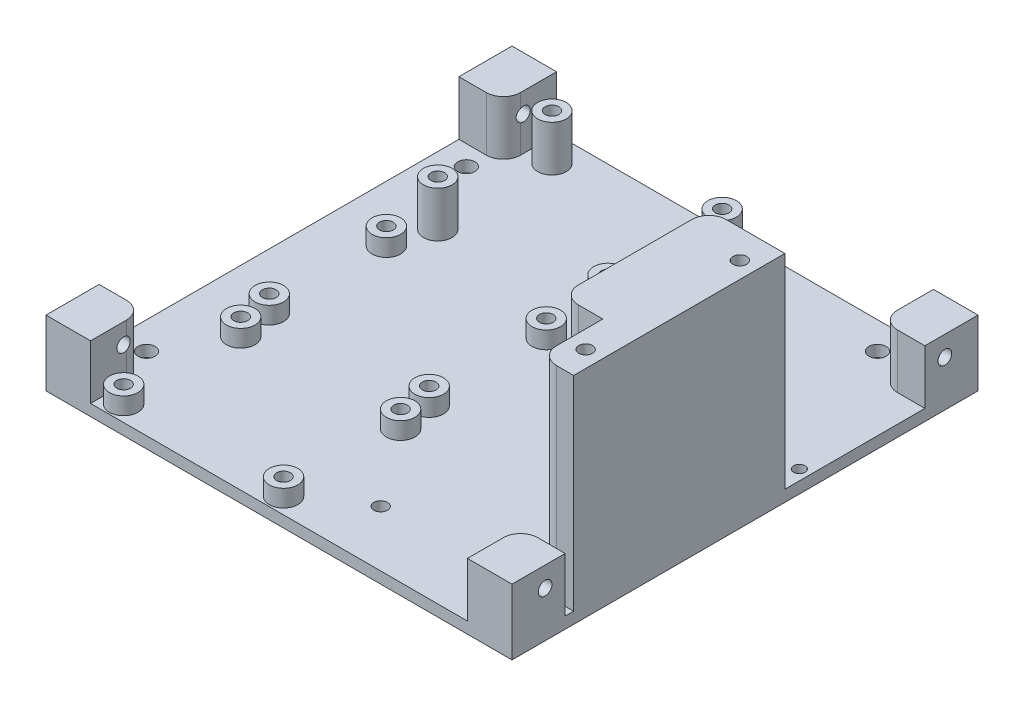
SolidWorks part; units mm, degrees
ref_plane "前基準面" through (0, 0, 0) normal (0, 0, 1) x (1, 0, 0)
ref_plane "上基準面" through (0, 0, 0) normal (0, 1, 0) x (1, 0, 0)
ref_plane "右基準面" through (0, 0, 0) normal (1, 0, 0) x (0, 0, -1)
sketch "草圖1" plane through (0, 0, 0) normal (0, 1, 0) x (1, 0, 0)
  line L1 (-45.7349, 16.1298) -> (36.2651, 16.1298)
  line L2 (-45.7349, 16.1298) -> (-45.7349, -65.8702)
  line L3 (-45.7349, -65.8702) -> (36.2651, -65.8702)
  line L4 (36.2651, 16.1298) -> (36.2651, -65.8702)
  dimension "D1" = 82
  dimension "D2" = 82
extrude "填料-伸長1" add sketch "草圖1" along normal blind 2
sketch "草圖3" plane through (0, 2, 0) normal (0, 1, 0) x (1, 0, 0)
  line L0 (36.2651, 16.1298) -> (-45.7349, 16.1298) construction
  line L1 (-45.7349, 16.1298) -> (-45.7349, -65.8702) construction
  line L2 (-45.7349, -65.8702) -> (36.2651, -65.8702) construction
  line L19 (36.2651, -65.8702) -> (36.2651, 16.1298) construction
  circle A18 centre (3.2651, -55.8702) radius 1.2
  circle A19 centre (19.5151, -25.6702) radius 1.2
  circle A20 centre (-33.7349, 11.1298) radius 1.2
  circle A21 centre (-3.9349, 11.1298) radius 1.2
  circle A22 centre (-33.7349, -8.8702) radius 1.2
  circle A23 centre (-3.9349, -8.8702) radius 1.2
  circle A24 centre (2.3151, 2.6298) radius 1
  circle A25 centre (-7.7349, -15.8702) radius 1.2
  circle A26 centre (-35.7349, -15.8702) radius 1.2
  circle A27 centre (-7.7349, -36.3702) radius 1.2
  circle A28 centre (-35.7349, -36.3702) radius 1.2
  circle A29 centre (-6.7349, -42.3702) radius 1.2
  circle A30 centre (-6.7349, -62.8702) radius 1.2
  circle A31 centre (-34.7349, -42.3702) radius 1.2
  circle A32 centre (-34.7349, -62.8702) radius 1.2
  circle A33 centre (34.2651, -13.5602) radius 1
  circle A34 centre (33.1651, -22.8782) radius 1.2
  circle A35 centre (33.1651, -49.8782) radius 1.2
  dimension "D5" = 2.4
  dimension "D9" = 20.5
  dimension "D10" = 12
  dimension "D11" = 7
  dimension "D12" = 16.19
  dimension "D14" = 7
  dimension "D16" = 20.5
  dimension "D17" = 5
  dimension "D22" = 28
  dimension "D23" = 10
  dimension "D24" = 10
  dimension "D25" = 11
  dimension "D26" = 11
  dimension "D27" = 6
  dimension "D28" = 20.5
  dimension "D29" = 20.5
  dimension "D34" = 16.25
  dimension "D35" = 12
  dimension "D36" = 2
  dimension "D37" = 2
  dimension "D38" = 29.8
  dimension "D39" = 29.8
  dimension "D41" = 20
  dimension "D18" = 6
  dimension "D19" = 28
  dimension "D15" = 20
  dimension "D20" = 28
  dimension "D21" = 28
  dimension "D32" = 30.2
  dimension "D33" = 10
  dimension "D43" = 31.95
  dimension "D44" = 2
  dimension "D46" = 27
  dimension "D47" = 3.1
  dimension "D48" = 10
  dimension "D13" = 13.5
  dimension "D42" = 5
extrude "除料-伸長2" cut sketch "草圖3" against normal through all and the other way through all contours A22 | A20 | A23 | A21
extrude "除料-伸長3" cut sketch "草圖3<3>" against normal through all both and the other way through all
sketch "草圖3<3>" plane through (0, 2, 0) normal (0, 1, 0) x (1, 0, 0) same geometry as "草圖3"
sketch "草圖4" plane through (0, 2, 0) normal (0, 1, 0) x (1, 0, 0)
  line L0 (36.2651, -65.8702) -> (36.2651, 16.1298) construction
  line L1 (36.2651, -17.8782) -> (22.7651, -17.8782)
  line L2 (36.2651, -17.8782) -> (36.2651, -54.8782)
  line L4 (22.7651, -17.8782) -> (22.7651, -43.7598)
  line L5 (22.7651, -43.7598) -> (30.0651, -43.7598)
  line L6 (30.0651, -43.7598) -> (30.0651, -54.8782)
  line L7 (30.0651, -54.8782) -> (36.2651, -54.8782)
  circle A3 centre (33.1651, -22.8782) radius 1.2
  circle A4 centre (33.1651, -49.8782) radius 1.2
  dimension "D2" = 2.4
  dimension "D4" = 2.4
  dimension "D1" = 6.2
  dimension "D3" = 13.5
extrude "填料-伸長2" add sketch "草圖4" along normal blind 35.75
sketch "草圖5" plane through (0, 2, 0) normal (0, 1, 0) x (1, 0, 0)
  line L0 (36.2651, 16.1298) -> (-45.7349, 16.1298) construction
  line L1 (36.2651, -17.8782) -> (36.2651, 16.1298) construction
  line L2 (-45.7349, -65.8702) -> (36.2651, -65.8702) construction
  line L3 (-45.7349, 16.1298) -> (-45.7349, -65.8702) construction
  line L5 (36.2651, 16.1298) -> (-45.7349, 16.1298) construction
  line L6 (36.2651, -65.8702) -> (36.2651, -54.8782) construction
  line L7 (-45.7349, -65.8702) -> (36.2651, -65.8702) construction
  circle A0 centre (26.7651, -49.8702) radius 1.5
  circle A1 centre (23.2651, 11.1298) radius 1.5
  circle A2 centre (-40.7349, 3.1298) radius 1.5
  circle A5 centre (-40.7349, -52.8702) radius 1.5
  dimension "D1" = 3
  dimension "D2" = 3
  dimension "D3" = 3
  dimension "D4" = 13
  dimension "D5" = 13
  dimension "D6" = 3
  dimension "D7" = 13
  dimension "D8" = 5
  dimension "D10" = 5
  dimension "D11" = 9.5
  dimension "D12" = 16
  dimension "D9" = 5
extrude "除料-伸長4" cut sketch "草圖5" against normal up to next
sketch "草圖7" plane through (0, 2, 0) normal (0, 1, 0) x (1, 0, 0)
  line L1 (-45.7349, 16.1298) -> (-37.7349, 16.1298)
  line L2 (-45.7349, 16.1298) -> (-45.7349, 6.6298)
  line L3 (-45.7349, 6.6298) -> (-37.7349, 6.6298)
  line L4 (-37.7349, 16.1298) -> (-37.7349, 6.6298)
  line L5 (36.2651, 16.1298) -> (28.2651, 16.1298)
  line L6 (36.2651, 16.1298) -> (36.2651, 6.6298)
  line L7 (36.2651, 6.6298) -> (28.2651, 6.6298)
  line L8 (28.2651, 16.1298) -> (28.2651, 6.6298)
  line L9 (36.2651, -65.8702) -> (28.2651, -65.8702)
  line L10 (36.2651, -65.8702) -> (36.2651, -56.3702)
  line L11 (36.2651, -56.3702) -> (28.2651, -56.3702)
  line L12 (28.2651, -65.8702) -> (28.2651, -56.3702)
  line L13 (-45.7349, -65.8702) -> (-37.7349, -65.8702)
  line L14 (-45.7349, -65.8702) -> (-45.7349, -56.3702)
  line L15 (-45.7349, -56.3702) -> (-37.7349, -56.3702)
  line L16 (-37.7349, -65.8702) -> (-37.7349, -56.3702)
  dimension "D1" = 9.5
  dimension "D2" = 8
  dimension "D3" = 9.5
  dimension "D4" = 9.5
  dimension "D5" = 9.5
extrude "填料-伸長3" add sketch "草圖7" along normal blind 9.5
sketch "草圖8" plane through (36.2651, 0, 0) normal (1, 0, 0) x (0, 0, -1)
  line L0 (6.6298, 11.5) -> (16.1298, 11.5) construction
  line L1 (6.6298, 11.5) -> (6.6298, 2) construction
  line L2 (-65.8702, 11.5) -> (-56.3702, 11.5) construction
  line L3 (-56.3702, 11.5) -> (-56.3702, 2) construction
  circle A0 centre (-59.8702, 8) radius 1.2
  circle A1 centre (10.1298, 8) radius 1.2
  dimension "D1" = 2.4
  dimension "D2" = 2.4
  dimension "D6" = 3.5
  dimension "D3" = 3.5
  dimension "D4" = 3.5
  dimension "D5" = 3.5
extrude "除料-伸長5" cut sketch "草圖8" against normal through all
sketch "草圖9" plane through (0, 2, 0) normal (0, 1, 0) x (1, 0, 0)
  line L30 (-45.5349, 15.9298) -> (-45.5349, -65.6702)
  line L31 (36.0651, 15.9298) -> (-45.5349, 15.9298)
  line L32 (36.0651, -65.6702) -> (36.0651, 15.9298)
  line L33 (-45.5349, -65.6702) -> (36.0651, -65.6702)
  line L34 (-45.5349, 15.9298) -> (-45.5349, -65.6702)
  line L35 (36.0651, 15.9298) -> (-45.5349, 15.9298)
  line L36 (36.0651, -65.6702) -> (36.0651, 15.9298)
  line L37 (-45.5349, -65.6702) -> (36.0651, -65.6702)
  line L42 (-45.7349, 16.1298) -> (-45.7349, -65.8702)
  line L43 (36.2651, 16.1298) -> (-45.7349, 16.1298)
  line L44 (36.2651, -65.8702) -> (36.2651, 16.1298)
  line L45 (-45.7349, -65.8702) -> (36.2651, -65.8702)
  line L46 (-45.7349, 16.1298) -> (-45.7349, -65.8702)
  line L47 (36.2651, 16.1298) -> (-45.7349, 16.1298)
  line L48 (36.2651, -65.8702) -> (36.2651, 16.1298)
  line L49 (-45.7349, -65.8702) -> (36.2651, -65.8702)
  dimension "D1" = 0.2
  dimension "D2" = 0
extrude "除料-伸長6" cut sketch "草圖9" against normal through all both and the other way through all
sketch "草圖10" plane through (0, 2, 0) normal (0, 1, 0) x (1, 0, 0)
  circle A0 centre (-33.7349, 11.1298) radius 2.5
  circle A1 centre (-3.9349, 11.1298) radius 2.5
  circle A2 centre (-33.7349, -8.8702) radius 2.5
  circle A3 centre (-3.9349, -8.8702) radius 2.5
  circle A4 centre (-33.7349, 11.1298) radius 1.2
  circle A5 centre (-33.7349, -8.8702) radius 1.2
  circle A6 centre (-3.9349, 11.1298) radius 1.2
  circle A7 centre (-3.9349, -8.8702) radius 1.2
  dimension "D1" = 5
extrude "填料-伸長4" add sketch "草圖10" along normal blind 8
sketch "草圖11" plane through (0, 2, 0) normal (0, 1, 0) x (1, 0, 0)
  circle A0 centre (-35.7349, -15.8702) radius 2.5
  circle A1 centre (-35.7349, -15.8702) radius 1.2
  circle A2 centre (-7.7349, -15.8702) radius 2.5
  circle A3 centre (-7.7349, -15.8702) radius 1.2
  circle A4 centre (-35.7349, -36.3702) radius 2.5
  circle A5 centre (-35.7349, -36.3702) radius 1.2
  circle A6 centre (-7.7349, -36.3702) radius 2.5
  circle A7 centre (-7.7349, -36.3702) radius 1.2
  circle A8 centre (-34.7349, -42.3702) radius 2.5
  circle A9 centre (-34.7349, -42.3702) radius 1.2
  circle A10 centre (-6.7349, -42.3702) radius 2.5
  circle A11 centre (-6.7349, -42.3702) radius 1.2
  circle A12 centre (-34.7349, -62.8702) radius 2.5
  circle A13 centre (-34.7349, -62.8702) radius 1.2
  circle A14 centre (-6.7349, -62.8702) radius 1.2
  circle A15 centre (-6.7349, -62.8702) radius 2.5
  dimension "D1" = 5
extrude "填料-伸長5" add sketch "草圖11" along normal blind 3
fillet "圓角1" radius 3 7 edges at (-37.7349, 6.75, -6.6298) (22.7651, 19.875, 17.8782) (22.7651, 19.875, 43.7598) (30.0651, 19.875, 54.8782) (28.2651, 6.75, 56.3702) (-37.7349, 6.75, 56.3702) (28.2651, 6.75, -6.6298)
